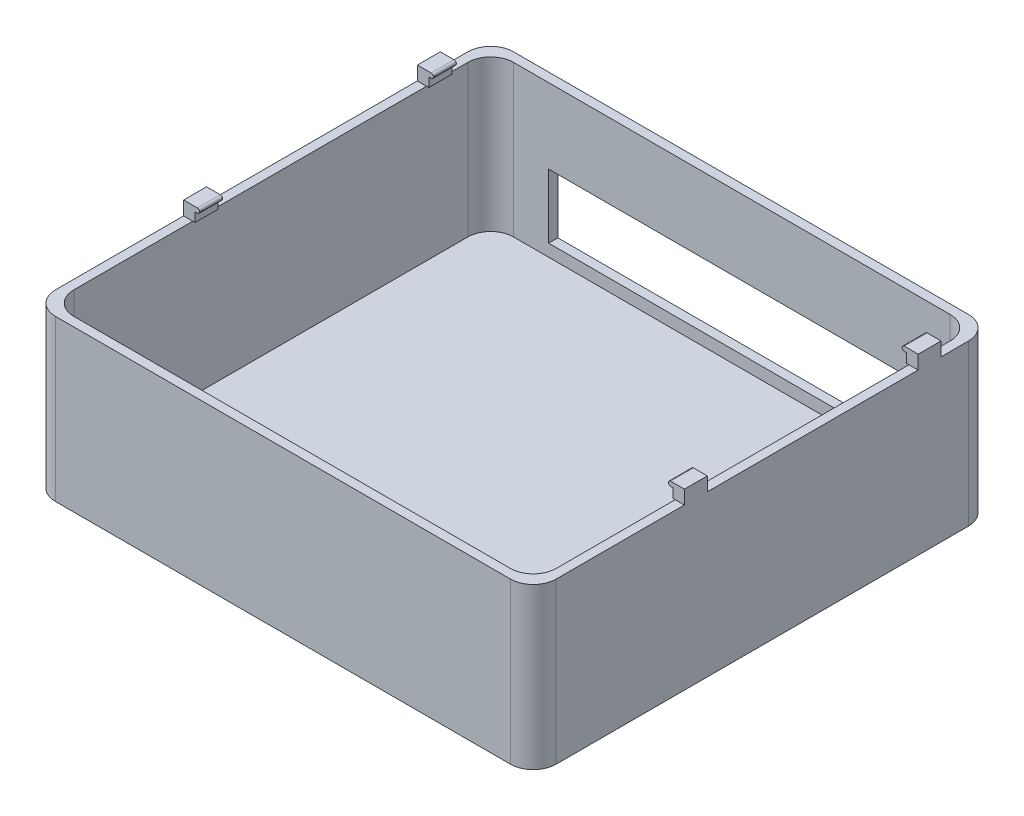
SolidWorks part; units mm, degrees
ref_plane "Front Plane" through (0, 0, 0) normal (0, 0, 1) x (1, 0, 0)
ref_plane "Top Plane" through (0, 0, 0) normal (0, 1, 0) x (1, 0, 0)
ref_plane "Right Plane" through (0, 0, 0) normal (1, 0, 0) x (0, 0, -1)
sketch "Sketch1" plane through (0, 0, 0) normal (0, 1, 0) x (1, 0, 0)
  line L1 (-54.65, 0) -> (54.65, 0)
  line L2 (-54.65, 0) -> (-54.65, -100)
  line L3 (-54.65, -100) -> (54.65, -100)
  line L4 (54.65, 0) -> (54.65, -100)
  point P4 (0, 0)
  dimension "D1" = 109.3
  dimension "D2" = 100
extrude "Boss-Extrude1" add sketch "Sketch1" along normal blind 35
sketch "Sketch2" plane through (0, 35, 0) normal (0, 1, 0) x (1, 0, 0)
  line L0 (-54.65, 0) -> (-54.65, -100) construction
  line L1 (-54.65, -10) -> (-52.15, -10)
  line L2 (-54.65, -10) -> (-54.65, -17)
  line L3 (-54.65, -17) -> (-52.15, -17)
  line L4 (-52.15, -10) -> (-52.15, -17)
  line L5 (54.65, 0) -> (-54.65, 0) construction
  line L6 (0, -55) -> (0, 55) construction
  line L7 (52.15, -10) -> (52.15, -17)
  line L8 (54.65, -17) -> (52.15, -17)
  line L9 (54.65, -10) -> (54.65, -17)
  line L10 (54.65, -10) -> (52.15, -10)
  line L11 (-70.5487, -39.01) -> (75.6401, -39.01) construction
  line L12 (54.65, 0) -> (-54.65, 0) construction
  line L13 (54.65, -68.02) -> (52.15, -68.02)
  line L14 (54.65, -68.02) -> (54.65, -61.02)
  line L15 (54.65, -61.02) -> (52.15, -61.02)
  line L16 (52.15, -68.02) -> (52.15, -61.02)
  line L17 (-52.15, -68.02) -> (-52.15, -61.02)
  line L18 (-54.65, -61.02) -> (-52.15, -61.02)
  line L19 (-54.65, -68.02) -> (-54.65, -61.02)
  line L20 (-54.65, -68.02) -> (-52.15, -68.02)
  dimension "D1" = 10
  dimension "D2" = 7
  dimension "D3" = 2.5
  dimension "D4" = 39.01
extrude "Boss-Extrude2" add sketch "Sketch2" along normal blind 3
sketch "Sketch3" plane through (-52.15, 0, 0) normal (1, 0, 0) x (0, 0, -1)
  line L0 (-10, 38) -> (-10, 35) construction
  line L1 (-17, 38) -> (-10, 38)
  line L2 (-17, 38) -> (-17, 37)
  line L3 (-17, 37) -> (-10, 37)
  line L4 (-10, 38) -> (-10, 37)
  line L5 (-61.02, 38) -> (-61.02, 35) construction
  line L6 (-68.02, 38) -> (-61.02, 38)
  line L7 (-68.02, 38) -> (-68.02, 37)
  line L8 (-68.02, 37) -> (-61.02, 37)
  line L9 (-61.02, 38) -> (-61.02, 37)
  dimension "D1" = 1
  dimension "D2" = 1
extrude "Boss-Extrude3" add sketch "Sketch3" along normal blind 1
sketch "Sketch4" plane through (52.15, 0, 0) normal (-1, 0, 0) x (0, 0, 1)
  line L1 (10, 38) -> (17, 38)
  line L2 (10, 38) -> (10, 37)
  line L3 (10, 37) -> (17, 37)
  line L4 (17, 38) -> (17, 37)
  line L6 (61.02, 38) -> (68.02, 38)
  line L7 (61.02, 38) -> (61.02, 37)
  line L8 (61.02, 37) -> (68.02, 37)
  line L9 (68.02, 38) -> (68.02, 37)
  line L10 (17, 38) -> (17, 35) construction
  line L12 (68.02, 38) -> (68.02, 35) construction
  dimension "D1" = 1
  dimension "D2" = 1
extrude "Boss-Extrude4" add sketch "Sketch4" along normal blind 1
fillet "Fillet1" radius 0.5 8 edges at (51.15, 38, 13.5) (51.15, 37, 13.5) (51.15, 37, 64.52) (51.15, 38, 64.52) (-51.15, 37, 13.5) (-51.15, 38, 13.5) (-51.15, 37, 64.52) (-51.15, 38, 64.52)
sketch "Sketch5" plane through (0, 35, 0) normal (0, 1, 0) x (1, 0, 0)
  line L0 (54.65, -61.02) -> (54.65, -17) construction
  line L1 (-52.65, -2) -> (52.65, -2)
  line L2 (-52.65, -2) -> (-52.65, -98)
  line L3 (-52.65, -98) -> (52.65, -98)
  line L4 (52.65, -2) -> (52.65, -98)
  line L5 (-54.65, -17) -> (-54.65, -61.02) construction
  line L6 (54.65, 0) -> (-54.65, 0) construction
  line L7 (-54.65, -100) -> (54.65, -100) construction
  dimension "D1" = 2
  dimension "D2" = 2
  dimension "D3" = 2
  dimension "D4" = 2
extrude "Cut-Extrude1" cut sketch "Sketch5" against normal offset from surface (33 mm away) 2 up to face at (0, 0, 50)
fillet "Fillet2" radius 5 8 edges at (54.65, 17.5, 0) (-54.65, 17.5, 0) (-54.65, 17.5, 100) (54.65, 17.5, 100) (52.65, 18.5, 98) (-52.65, 18.5, 98) (52.65, 18.5, 2) (-52.65, 18.5, 2)
sketch "Sketch6" plane through (-54.65, 0, 0) normal (-1, 0, 0) x (0, 0, 1)
  line L1 (10, 38) -> (11, 38)
  line L2 (10, 38) -> (10, 35)
  line L3 (10, 35) -> (11, 35)
  line L4 (11, 38) -> (11, 35)
  line L5 (17, 38) -> (16, 38)
  line L6 (17, 38) -> (17, 35)
  line L7 (17, 35) -> (16, 35)
  line L8 (16, 38) -> (16, 35)
  line L9 (61.02, 38) -> (62.02, 38)
  line L10 (61.02, 38) -> (61.02, 35)
  line L11 (61.02, 35) -> (62.02, 35)
  line L12 (62.02, 38) -> (62.02, 35)
  line L18 (68.02, 38) -> (67.02, 38)
  line L19 (68.02, 38) -> (68.02, 35)
  line L20 (68.02, 35) -> (67.02, 35)
  line L21 (67.02, 38) -> (67.02, 35)
  dimension "D1" = 1
  dimension "D2" = 3
  dimension "D3" = 3
  dimension "D4" = 1
  dimension "D5" = 1
  dimension "D6" = 3
  dimension "D7" = 1
  dimension "D8" = 3
extrude "Cut-Extrude2" cut sketch "Sketch6" against normal through all
sketch "Sketch7" plane through (0, 0, 0) normal (0, 0, -1) x (-1, 0, 0)
  line L1 (-40, 18.661) -> (40, 18.661)
  line L2 (-40, 18.661) -> (-40, 4.661)
  line L3 (-40, 4.661) -> (40, 4.661)
  line L4 (40, 18.661) -> (40, 4.661)
  point P4 (0, 18.661)
  dimension "D1" = 14
  dimension "D2" = 80
  dimension "D3" = 0
extrude "Cut-Extrude3" cut sketch "Sketch7" against normal up to next
